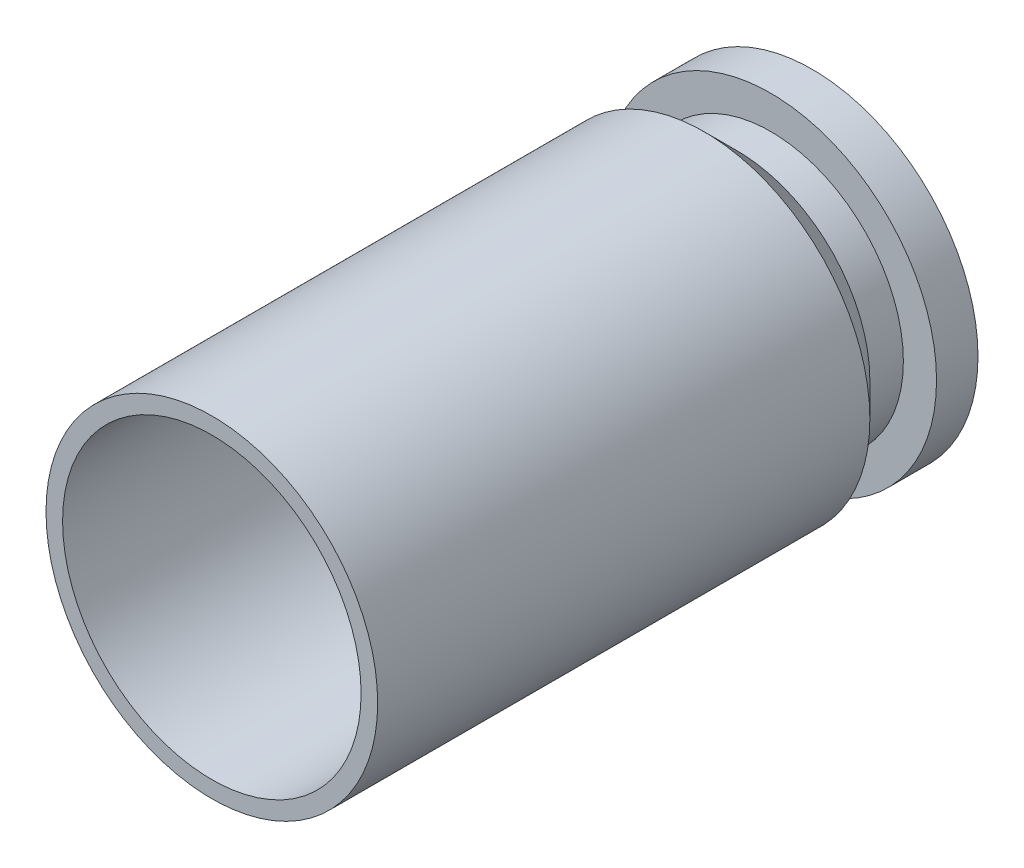
SolidWorks part; units mm, degrees
material "Nickel"
ref_plane "Front Plane" through (0, 0, 0) normal (0, 0, 1) x (1, 0, 0)
ref_plane "Top Plane" through (0, 0, 0) normal (0, 1, 0) x (1, 0, 0)
ref_plane "Right Plane" through (0, 0, 0) normal (1, 0, 0) x (0, 0, -1)
sketch "Sketch1" plane through (0, 0, 0) normal (1, 0, 0) x (0, 0, -1)
  line L0 (16.85, -5) -> (18.1, -5)
  line L1 (0, 0) -> (18.1, 0)
  line L2 (0, 0) -> (0, -5)
  line L3 (0, -5) -> (16.84, -5)
  line L4 (18.1, 0) -> (18.1, -5)
  line L6 (16.85, -5) -> (16.85, -4)
  line L7 (16.85, -4) -> (16.84, -4)
  line L8 (16.84, -5) -> (16.84, -4)
  dimension "D1" = 18.1
  dimension "D2" = 5
  dimension "D3" = 1.25
  dimension "D4" = 1.26
  dimension "D5" = 1
revolve "Revolve1" add sketch "Sketch1" angle 360 about L1
sketch "Sketch2" plane through (0, 0, 0) normal (0, 0, 1) x (1, 0, 0)
  circle A0 centre (0, 0) radius 4.5
  dimension "D1" = 9
extrude "Cut-Extrude1" cut sketch "Sketch2" against normal blind 11
chamfer "Chamfer2" distance 2 angle 45 1 edges at (5, 0, -16.84)
